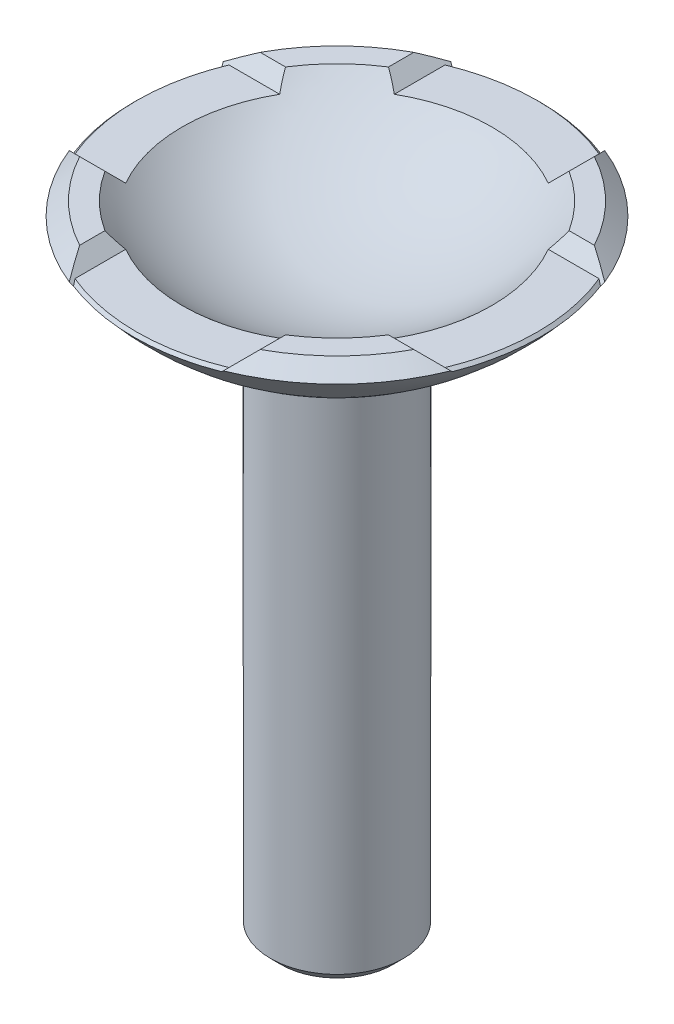
SolidWorks part; units mm, degrees
ref_plane "Front Plane" through (0, 0, 0) normal (0, 0, 1) x (1, 0, 0)
ref_plane "Top Plane" through (0, 0, 0) normal (0, 1, 0) x (1, 0, 0)
ref_plane "Right Plane" through (0, 0, 0) normal (1, 0, 0) x (0, 0, -1)
sketch "Sketch2" plane through (0, 0, 0) normal (0, 0, 1) x (1, 0, 0)
  line L0 (0, 0) -> (0, 210.8246) construction
  line L1 (0, 0) -> (-12.5, 0)
  line L2 (-12.5, 0) -> (-12.5, 100)
  line L3 (-38.737, 116.7983) -> (-33.3741, 121.2983)
  line L4 (0, 0) -> (0, 105.4123)
  arc A0 (-12.5, 100) -> (-38.737, 116.7983) centre (0, 148.4123) cw
  arc A1 (0, 105.4123) -> (-33.3741, 121.2983) centre (0, 148.4123) cw
  dimension "D1" = 50
  dimension "D2" = 7
  dimension "D3" = 100
  dimension "D4" = 12.5
  dimension "D5" = 130
  dimension "D6" = 4.5
revolve "Revolve1" add sketch "Sketch2" angle 360 about L4
sketch "Sketch3" plane through (0, 0, 0) normal (1, 0, 0) x (0, 0, -1)
  line L0 (-19, 121.2983) -> (19, 121.2983)
  line L1 (33.3741, 121.2983) -> (-33.3741, 121.2983) construction
  line L2 (19, 121.2983) -> (14.5, 116.7983)
  line L3 (38.737, 116.7983) -> (-38.737, 116.7983) construction
  line L4 (14.5, 116.7983) -> (-14.5, 116.7983)
  line L5 (-14.5, 116.7983) -> (-19, 121.2983)
  point P7 (0, 116.7983)
  point P9 (0, 121.2983)
  dimension "D1" = 29
  dimension "D2" = 135
extrude "Cut-Extrude1" cut sketch "Sketch3" against normal through all both and the other way through all
pattern_circular "CirPattern1" count 2 over 90 of "Cut-Extrude1"
sketch "Sketch4" plane through (0, 0, 0) normal (1, 0, 0) x (0, 0, -1)
  line L0 (-19, 121.2983) -> (-27.4378, 121.2983) construction
  line L1 (35.8464, 119.2983) -> (-35.8464, 119.2983)
  line L2 (35.8464, 119.2983) -> (35.8464, 126.8363)
  line L3 (35.8464, 126.8363) -> (-35.8464, 126.8363)
  line L4 (-35.8464, 119.2983) -> (-35.8464, 126.8363)
  line L5 (35.8464, 119.2983) -> (-35.8464, 126.8363) construction
  line L6 (35.8464, 126.8363) -> (-35.8464, 119.2983) construction
  point P0 (0, 123.0673)
  point P7 (0, 0)
  dimension "D1" = 2
extrude "Cut-Extrude2" cut sketch "Sketch4" against normal through all both and the other way through all
chamfer "Chamfer1" distance 1 angle 45 4 edges at (-38.737, 116.7983, 0) (38.737, 116.7983, 0) (0, 116.7983, 38.737) (0, 116.7983, -38.737)
chamfer "Chamfer2" distance 2 angle 45 1 edges at (0, 0, -12.5)
